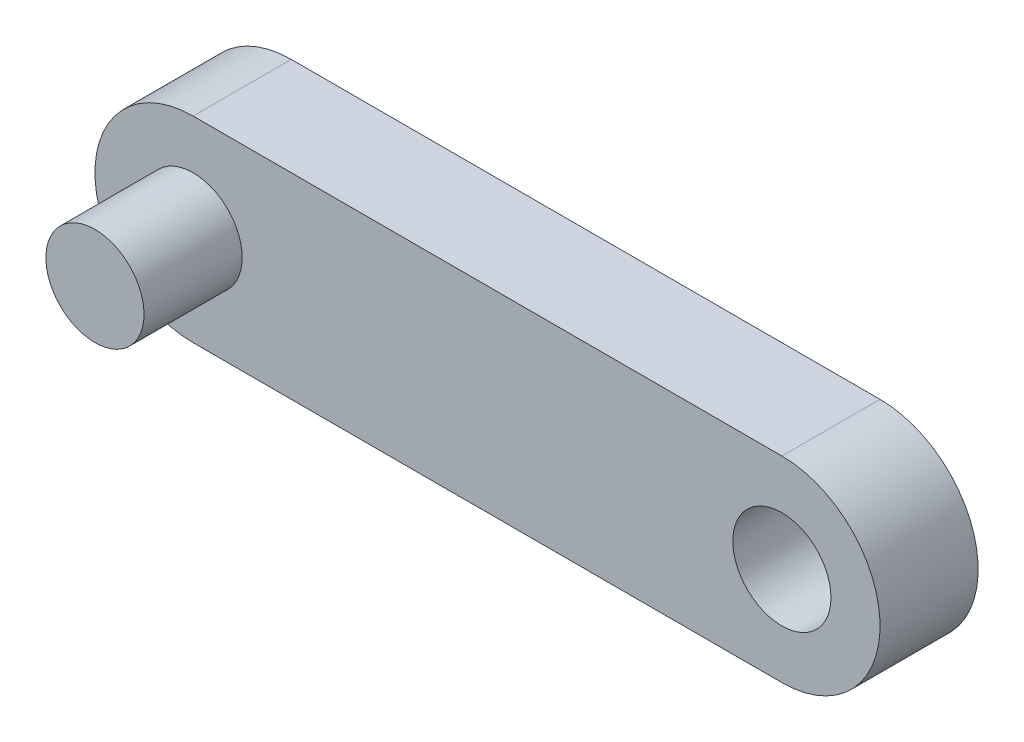
SolidWorks part; units mm, degrees
ref_plane "Front Plane" through (0, 0, 0) normal (0, 0, 1) x (1, 0, 0)
ref_plane "Top Plane" through (0, 0, 0) normal (0, 1, 0) x (1, 0, 0)
ref_plane "Right Plane" through (0, 0, 0) normal (1, 0, 0) x (0, 0, -1)
sketch "Sketch1" plane through (0, 0, 0) normal (0, 0, 1) x (1, 0, 0)
  line L0 (-15, 0) -> (15, 0) construction
  line L1 (-15, 5) -> (15, 5)
  line L2 (-15, -5) -> (15, -5)
  arc A0 (-15, 5) -> (-15, -5) centre (-15, 0) ccw
  arc A1 (15, -5) -> (15, 5) centre (15, 0) ccw
  circle A2 centre (-15, 0) radius 2.5
  circle A3 centre (15, 0) radius 2.5
  point P2 (0, 0)
  dimension "D1" = 5
  dimension "D2" = 5
  dimension "D3" = 30
extrude "Boss-Extrude1" add sketch "Sketch1" along normal blind 5
extrude "Boss-Extrude2" add sketch "Sketch1<2>" along normal blind 10 contours A2 region at (-15, 0, 0)
sketch "Sketch1<2>" plane through (0, 0, 0) normal (0, 0, 1) x (1, 0, 0) same geometry as "Sketch1"
